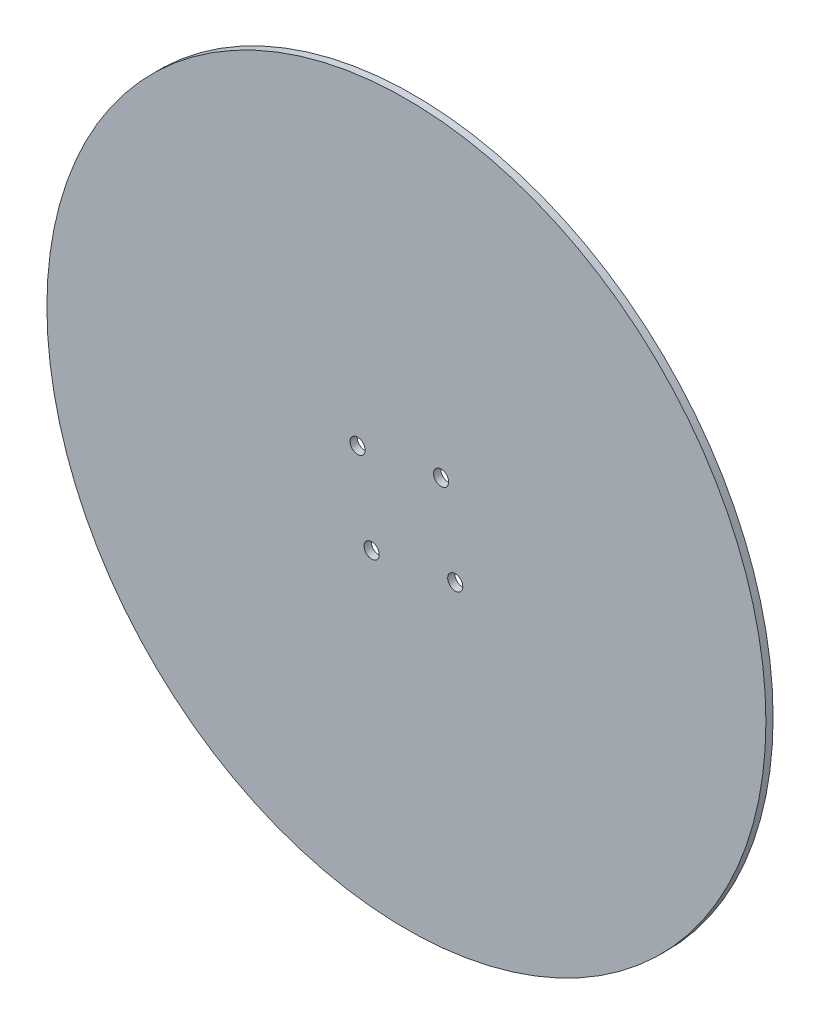
SolidWorks part; units mm, degrees
ref_plane "Front Plane" through (0, 0, 0) normal (0, 0, 1) x (1, 0, 0)
ref_plane "Top Plane" through (0, 0, 0) normal (0, 1, 0) x (1, 0, 0)
ref_plane "Right Plane" through (0, 0, 0) normal (1, 0, 0) x (0, 0, -1)
sketch "Sketch1" plane through (0, 0, 0) normal (0, 0, 1) x (1, 0, 0)
  line L0 (0, 0) -> (0, 140) construction
  line L1 (0, 140) -> (0, 150) construction
  line L2 (-12.5, 140) -> (12.5, 140) construction
  circle A0 centre (0, 0) radius 150
  circle A5 centre (20.3733, -14.4889) radius 3.15
  circle A6 centre (-14.4889, -20.3733) radius 3.15
  circle A7 centre (-20.3733, 14.4889) radius 3.15
  circle A8 centre (14.4889, 20.3733) radius 3.15
  point P9 (0, 140)
  point P21 (0, 0)
  dimension "D1" = 300
  dimension "D2" = 6.3
  dimension "D4" = 6.3
  dimension "D3" = 6.3
  dimension "D6" = 6.3
  dimension "D5" = 140
extrude "Boss-Extrude2" add sketch "Sketch1" along normal blind 3
